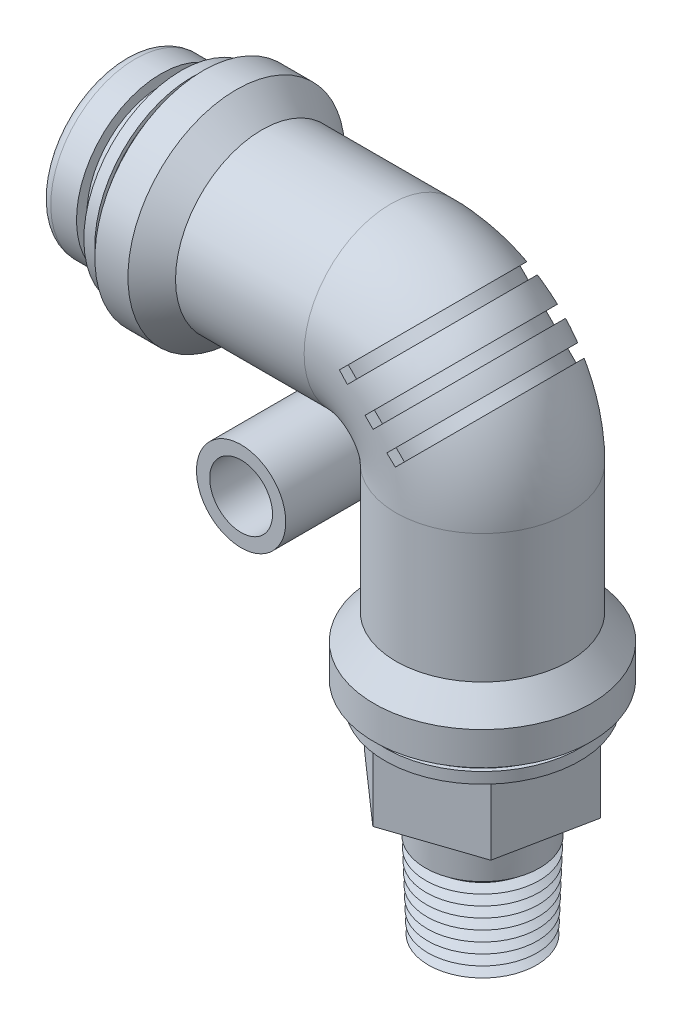
SolidWorks part; units mm, degrees
note: '?' marks a value the reader was unsure of.
ref_plane "Front Plane" through (0, 0, 0) normal (0, 0, 1) x (1, 0, 0)
ref_plane "Top Plane" through (0, 0, 0) normal (0, 1, 0) x (1, 0, 0)
ref_plane "Right Plane" through (0, 0, 0) normal (1, 0, 0) x (0, 0, -1)
sketch "Sketch1" plane through (0, 0, 0) normal (0, 0, 1) x (1, 0, 0)
  line L0 (-15.24, 0) -> (-6.35, 0)
  line L1 (0, -6.35) -> (0, -15.24)
  arc A0 (0, -6.35) -> (-6.35, 0) centre (-6.35, -6.35) ccw
  point P6 (0, 0)
  dimension "D3" = 6.35
  dimension "D1" = 15.24
  dimension "D2" = 15.24
ref_plane "Plane2" through (-15.24, 0, 0) normal (1, 0, 0) x (0, 0, -1)
other "Structural Member1"
ref_plane "Plane1" through (-15.24, 0, 0) normal (1, 0, 0) x (0, 1, 0)
sketch "Sketch11" plane through (-15.24, 0, 0) normal (1, 0, 0) x (0, 1, 0)
  circle A0 centre (0, 0) radius 5.08
  circle A1 centre (0, 0) radius 5.9817
  point P5 (0, 0)
  dimension "In_dia" = 10.16
  dimension "Out_dia" = 11.9634
sketch "Sketch21" plane through (0, 0, 0) normal (0, 0, 1) x (1, 0, 0)
  line L0 (-15.24, 0) -> (-20.828, 0)
  line L1 (-15.24, 5.9817) -> (-15.24, -5.9817) construction
  line L2 (-19.304, 6.4516) -> (-19.304, 7.493)
  line L3 (-19.304, 7.493) -> (-17.018, 7.493)
  line L4 (-17.018, 7.493) -> (-15.24, 5.9817)
  line L5 (-15.24, 5.9817) -> (-15.24, 0)
  line L12 (-20.066, 6.731) -> (-20.828, 6.731)
  line L13 (-20.828, 6.731) -> (-20.828, 0)
  line L15 (-20.066, 6.731) -> (-20.066, 6.4516)
  line L16 (-20.066, 6.4516) -> (-19.304, 6.4516)
  dimension "D1" = 7.493
  dimension "D2" = 5.588
  dimension "D3" = 6.731
  dimension "D4" = 0.762
  dimension "D5" = 0.762
  dimension "D6" = 1.778
  dimension "D7" = 6.4516
revolve "Revolve1" add sketch "Sketch21" angle 360 about L0
sketch "Sketch22" plane through (0, 0, 0) normal (0, 0, 1) x (1, 0, 0)
  line L0 (-15.24, 0) -> (-20.828, 0)
  line L2 (-19.304, 6.4516) -> (-19.304, 7.493)
  line L3 (-19.304, 7.493) -> (-17.018, 7.493)
  line L4 (-17.018, 7.493) -> (-15.24, 5.9817)
  line L5 (-15.24, 5.9817) -> (-15.24, 0)
  line L12 (-20.066, 6.731) -> (-20.828, 6.731)
  line L13 (-20.828, 6.731) -> (-20.828, 0)
  line L15 (-20.066, 6.731) -> (-20.066, 6.4516)
  line L16 (-20.066, 6.4516) -> (-19.304, 6.4516)
  dimension "D1" = 7.493
  dimension "D2" = 5.588
  dimension "D3" = 6.731
  dimension "D4" = 0.762
  dimension "D5" = 0.762
  dimension "D6" = 1.778
  dimension "D7" = 6.4516
sketch "Sketch23" plane through (0, 0, 0) normal (0, 0, 1) x (1, 0, 0)
  line L0 (0, -15.24) -> (0, -20.828)
  line L1 (-5.9817, -6.35) -> (-5.9817, -15.24) construction
  line L2 (-6.4516, -19.304) -> (-7.493, -19.304)
  line L3 (-7.493, -19.304) -> (-7.493, -17.018)
  line L4 (-7.493, -17.018) -> (-5.9817, -15.24)
  line L5 (-5.9817, -15.24) -> (0, -15.24)
  line L6 (-5.9817, -15.24) -> (5.9817, -15.24) construction
  line L12 (-6.731, -20.066) -> (-6.731, -20.828)
  line L13 (-6.731, -20.828) -> (0, -20.828)
  line L15 (-6.731, -20.066) -> (-6.4516, -20.066)
  line L16 (-6.4516, -20.066) -> (-6.4516, -19.304)
  dimension "D1" = 7.493
  dimension "D2" = 5.588
  dimension "D3" = 6.731
  dimension "D4" = 0.762
  dimension "D5" = 0.762
  dimension "D6" = 1.778
  dimension "D7" = 6.4516
  dimension "D8" = 90
  dimension "D9" = 90
  dimension "D10" = 0.762
  dimension "D11" = 1.0414
revolve "Revolve2" add sketch "Sketch23" angle 360 about L0
sketch "Sketch24" plane through (-20.828, 0, 0) normal (-1, 0, 0) x (0, 0, 1)
  circle A0 centre (0, 0) radius 5.08
  circle A1 centre (0, 0) radius 5.08 construction
extrude "Extrude4" cut sketch "Sketch24" against normal blind 11.7602
sketch "Sketch25" plane through (0, -20.828, 0) normal (0, -1, 0) x (1, 0, 0)
  circle A0 centre (0, 0) radius 5.08
  circle A1 centre (0, 0) radius 5.08 construction
extrude "Extrude5" cut sketch "Sketch25" against normal blind 9.2202
sketch "Sketch26" plane through (0, 0, 0) normal (0, 0, 1) x (1, 0, 0)
  line L2 (-15.24, -5.9817) -> (-6.35, -5.9817) construction
  line L3 (-5.9817, -6.35) -> (-5.9817, -15.24) construction
  circle A0 centre (-8.1534, -8.1534) radius 3.0861
  circle A1 centre (-8.1534, -8.1534) radius 2.1717
  dimension "D1" = 6.1722
  dimension "D2" = 4.3434
extrude "Extrude6" add sketch "Sketch26" along normal mid plane 17.0688 separate body
sketch "Sketch15" plane through (0, 0, 0) normal (0, 0, 1) x (1, 0, 0)
  line L2 (-6.35, -6.35) -> (0, 0) construction
ref_plane "Plane7" through (0, 0, 0) normal (0.7071, -0.7071, 0) x (0, 0, -1)
sketch "Sketch16" plane through (0, 0, 0) normal (0.7071, -0.7071, 0) x (0, 0, -1)
  line L0 (-6.35, -2.6303) -> (-5.334, -2.6303)
  line L1 (5.334, -2.6303) -> (6.35, -2.6303)
  arc A0 (6.35, -2.6303) -> (-6.35, -2.6303) centre (0, -2.6303) ccw
  arc A2 (5.334, -2.6303) -> (-5.334, -2.6303) centre (0, -2.6303) ccw
  arc A3 (5.9817, -2.6303) -> (-5.9817, -2.6303) centre (0, -2.6303) ccw construction
  dimension "D1" = 6.35
  dimension "D2" = 5.334
extrude "Extrude1" cut sketch "Sketch16" against normal mid plane 0.7925
ref_axis "Axis1" through (-8.1534, -8.1534, 8.5344) along (0, 0, -1)?
ref_plane "Plane8" through (1.7961, -1.7961, 0) normal (0.7071, -0.7071, 0) x (0, 0, -1)
ref_plane "Plane9" through (-1.7961, 1.7961, 0) normal (0.7071, -0.7071, 0) x (0, 0, -1)
sketch "Sketch27" plane through (-1.7961, 1.7961, 0) normal (0.7071, -0.7071, 0) x (0, 0, -1)
  line L0 (-5.334, -2.6303) -> (-6.35, -2.6303)
  line L1 (5.334, -2.6303) -> (6.35, -2.6303)
  arc A0 (5.334, -2.6303) -> (-5.334, -2.6303) centre (0, -2.6303) ccw
  arc A1 (6.35, -2.6303) -> (-6.35, -2.6303) centre (0, -2.6303) ccw
extrude "Extrude7" cut sketch "Sketch27" against normal mid plane 0.8128
sketch "Sketch28" plane through (1.7961, -1.7961, 0) normal (0.7071, -0.7071, 0) x (0, 0, -1)
  line L0 (-6.35, -2.6303) -> (-5.334, -2.6303)
  line L1 (5.334, -2.6303) -> (6.35, -2.6303)
  arc A0 (5.334, -2.6303) -> (-5.334, -2.6303) centre (0, -2.6303) ccw
  arc A1 (6.35, -2.6303) -> (-6.35, -2.6303) centre (0, -2.6303) ccw
extrude "Extrude8" cut sketch "Sketch28" against normal blind 0.8128
sketch "Sketch30" plane through (0, 0, 0) normal (0, 0, 1) x (1, 0, 0)
  line L0 (-20.828, 0) -> (-24.765, 0) construction
  line L1 (-20.828, 6.731) -> (-20.828, -6.731) construction
  line L2 (-24.765, 3.175) -> (-24.765, 5.08)
  line L3 (-24.003, 5.842) -> (-22.225, 5.842)
  line L4 (-22.225, 5.842) -> (-22.225, 5.1266)
  line L5 (-22.225, 5.1266) -> (-20.828, 5.08)
  line L6 (-20.828, 5.08) -> (-20.828, 3.175)
  line L7 (-20.828, 3.175) -> (-24.765, 3.175)
  arc A0 (-24.765, 5.08) -> (-24.003, 5.842) centre (-24.003, 5.08) cw
  dimension "D1" = 0.762
  dimension "D2" = 5.842
  dimension "D3" = 2.54
  dimension "D4" = 3.937
  dimension "D5" = 3.175
revolve "Revolve3" add sketch "Sketch30" angle 360 about L0
sketch "Sketch31" plane through (0, -20.828, 0) normal (0, -1, 0) x (1, 0, 0)
  line L1 (1.2702, -6.3113) -> (6.1008, -2.0556)
  line L2 (6.1008, -2.0556) -> (4.8306, 4.2556)
  line L3 (4.8306, 4.2556) -> (-1.2702, 6.3113)
  line L4 (-1.2702, 6.3113) -> (-6.1008, 2.0556)
  line L5 (-6.1008, 2.0556) -> (-4.8306, -4.2556)
  line L6 (-4.8306, -4.2556) -> (1.2702, -6.3113)
  circle A0 centre (0, 0) radius 5.5753 construction
  dimension "D1" = 11.1506
extrude "Extrude9" add sketch "Sketch31" along normal blind 4.7625 separate body
sketch "Sketch32" plane through (0, -25.5905, 0) normal (0, -1, 0) x (1, 0, 0)
  circle A0 centre (0, 0) radius 4.0513
  dimension "D1" = 8.1026
extrude "Extrude10" add sketch "Sketch32" along normal blind 9.3726 draft 2 separate body
sketch "Sketch33" plane through (0, -34.9631, 0) normal (0, -1, 0) x (1, 0, 0)
  circle A0 centre (0, 0) radius 1.7145
  dimension "D1" = 3.429
extrude "Extrude11" cut sketch "Sketch33" against normal blind 16.9926
sketch "Sketch34" plane through (0, 0, 0) normal (0, 0, 1) x (1, 0, 0)
  line L0 (-3.4053, -25.8952) -> (-3.0886, -34.9631) construction
  line L1 (-3.724, -34.9631) -> (3.724, -34.9631) construction
  line L3 (-4.0513, -25.5905) -> (-3.724, -34.9631) construction
  line L4 (-3.0886, -34.9631) -> (-3.7386, -34.5449)
  line L5 (-3.7386, -34.5449) -> (-3.1144, -34.2235)
  line L6 (-3.1144, -34.2235) -> (-3.7644, -33.8053)
  line L7 (-3.1419, -33.4359) -> (-3.79, -33.072)
  line L8 (-3.7644, -33.8053) -> (-3.1419, -33.4359)
  line L9 (-3.8157, -32.3383) -> (-3.1927, -31.9829)
  line L10 (-3.1927, -31.9829) -> (-3.8413, -31.604)
  line L11 (-3.1674, -32.7081) -> (-3.8157, -32.3383)
  line L12 (-3.79, -33.072) -> (-3.1674, -32.7081)
  line L13 (-3.2176, -31.2706) -> (-3.8671, -30.8667)
  line L14 (-3.2918, -29.1452) -> (-4.334, -28.3242)
  line L15 (-3.8928, -30.1282) -> (-3.271, -29.7406)
  line L16 (-3.8413, -31.604) -> (-3.2176, -31.2706)
  line L17 (-3.9184, -29.3955) -> (-3.2918, -29.1452)
  line L18 (-3.271, -29.7406) -> (-3.9184, -29.3955)
  line L19 (-3.2431, -30.5398) -> (-3.8928, -30.1282)
  line L20 (-3.8671, -30.8667) -> (-3.2431, -30.5398)
  line L21 (0, -25.8863) -> (0, -35.5945) construction
  line L22 (-4.334, -34.9631) -> (-4.334, -28.3242)
  line L23 (-3.0886, -34.9631) -> (-4.334, -34.9631)
  dimension "D1" = 0.635
  dimension "D2" = 60
  dimension "D3" = 60
  dimension "D4" = 60
  dimension "D5" = 60
  dimension "D6" = 60
  dimension "D7" = 60
  dimension "D8" = 60
  dimension "D9" = 60
revolve "Cut-Revolve1" cut sketch "Sketch34" angle 360 about L21
